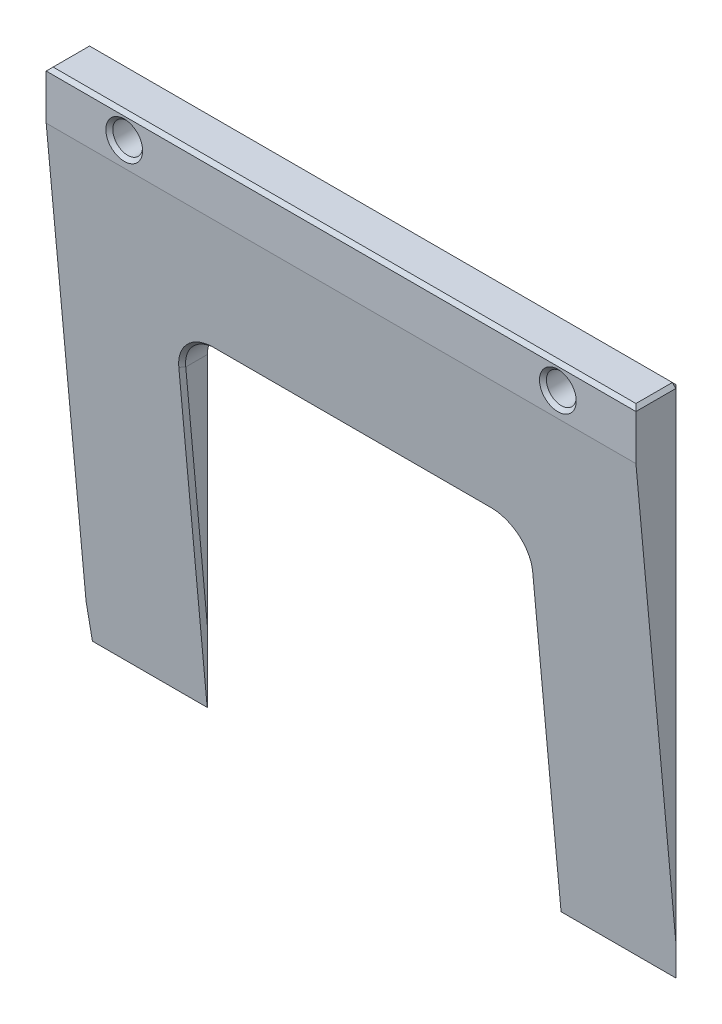
SolidWorks part; units mm, degrees
material "1060 Alloy"
ref_plane "Front Plane" through (0, 0, 0) normal (0, 0, 1) x (1, 0, 0)
ref_plane "Top Plane" through (0, 0, 0) normal (0, 1, 0) x (1, 0, 0)
ref_plane "Right Plane" through (0, 0, 0) normal (1, 0, 0) x (0, 0, -1)
sketch "Sketch1" plane through (0, 0, 0) normal (0, 0, 1) x (1, 0, 0)
  line L0 (25.4, -38.1) -> (43.18, -38.1)
  line L1 (-43.18, -38.1) -> (-25.4, -38.1)
  line L2 (-43.18, -38.1) -> (-43.18, 38.1)
  line L3 (-43.18, 38.1) -> (43.18, 38.1)
  line L4 (43.18, -38.1) -> (43.18, 38.1)
  line L5 (-43.18, -38.1) -> (43.18, 38.1) construction
  line L6 (-43.18, 38.1) -> (43.18, -38.1) construction
  line L7 (-25.4, 12.7) -> (25.4, 12.7)
  line L8 (-25.4, 12.7) -> (-25.4, -38.1)
  line L10 (25.4, 12.7) -> (25.4, -38.1)
  line L11 (-31.75, 34.544) -> (31.75, 34.544) construction
  circle A0 centre (-31.75, 34.544) radius 2.1828
  circle A1 centre (31.75, 34.544) radius 2.1828
  point P0 (0, 0)
  point P14 (0, 34.544)
  point P15 (0, 38.1)
  dimension "D6" = 4.3656
  dimension "D1" = 86.36
  dimension "D2" = 76.2
  dimension "D3" = 50.8
  dimension "D4" = 50.8
  dimension "D5" = 17.78
  dimension "D7" = 3.556
  dimension "D8" = 63.5
extrude "Boss-Extrude1" add sketch "Sketch1" along normal blind 6.35
sketch "Sketch2" plane through (43.18, 0, 0) normal (1, 0, 0) x (0, 0, -1)
  line L0 (-6.35, 30.988) -> (0, -38.1)
  line L1 (-6.35, -38.1) -> (-6.35, 38.1) construction
  line L2 (-6.35, -38.1) -> (0, -38.1) construction
  line L3 (0, -38.1) -> (0, 38.1) construction
  line L7 (0, -38.1) -> (-6.35, -38.1)
  line L8 (-6.35, -38.1) -> (-6.35, 30.988)
  line L9 (-6.35, 38.1) -> (0, 38.1) construction
  dimension "D1" = 7.112
extrude "Cut-Extrude1" cut sketch "Sketch2" against normal through all
fillet "Fillet1" radius 5.08 2 edges at (25.4, 12.7, 2.3346) (-25.4, 12.7, 2.3346)
chamfer "Chamfer1" distance 0.508 angle 45 17 edges at (33.9328, 34.544, 0) (-34.29, -38.1, 0) (-25.4, -15.24, 0) (-23.9121, 11.2121, 0) (0, 12.7, 0) (23.9121, 11.2121, 0) (25.4, -15.24, 0) (34.29, -38.1, 0) (43.18, 38.1, 3.175) (0, 38.1, 6.35) (-43.18, 38.1, 3.175) (-43.18, 0, 0) (0, 38.1, 0) (43.18, 0, 0) (-29.5672, 34.544, 0) (-29.5672, 34.544, 6.35) (33.9328, 34.544, 6.35)
chamfer "Chamfer2" distance 0.508 angle 45 5 edges at (25.4, -12.4765, 2.3551) (23.9121, 11.2121, 4.5324) (0, 12.7, 4.6691) (-23.9121, 11.2121, 4.5324) (-25.4, -12.4765, 2.3551)
